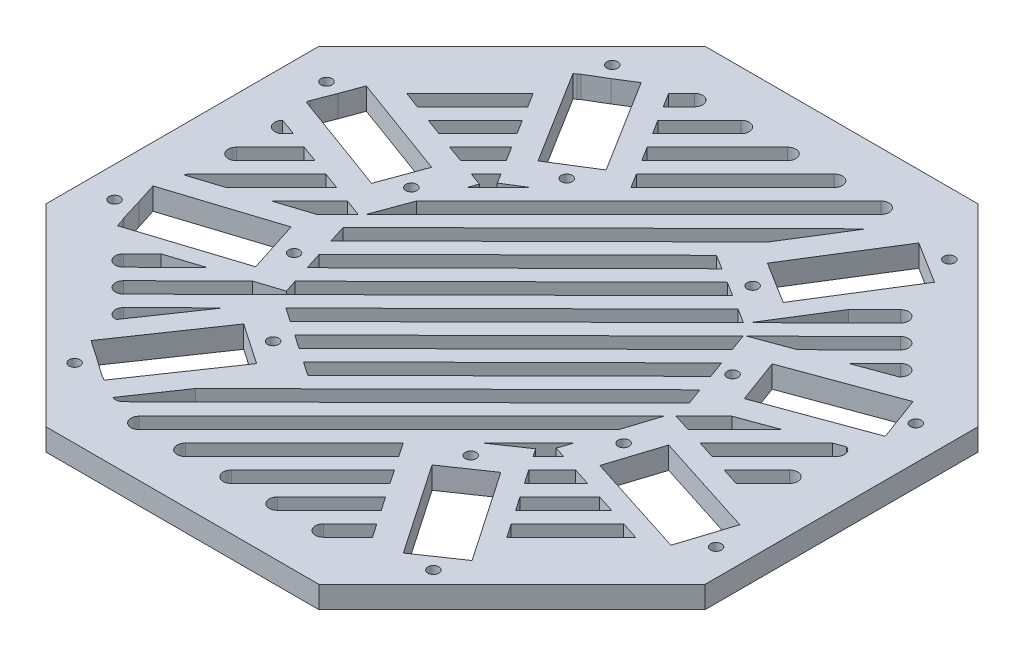
SolidWorks part; units mm, degrees
other "Camera1"
ref_plane "Front Plane" through (0, 0, 0) normal (0, 0, 1) x (1, 0, 0)
ref_plane "Top Plane" through (0, 0, 0) normal (0, 1, 0) x (1, 0, 0)
ref_plane "Right Plane" through (0, 0, 0) normal (1, 0, 0) x (0, 0, -1)
sketch "Sketch" plane through (0, 0, 0) normal (0, 1, 0) x (1, 0, 0)
  line L0 (0, 0) -> (60, 0) construction
  line L1 (0, 0) -> (60, 24.8528) construction
  line L2 (-6.8563, 54.06) -> (-15.6607, 52.1942)
  line L3 (60, 24.8528) -> (24.8528, 60)
  line L4 (24.8528, 60) -> (-24.8528, 60)
  line L5 (-24.8528, 60) -> (-60, 24.8528)
  line L6 (-60, 24.8528) -> (-60, -24.8528)
  line L7 (-60, -24.8528) -> (-24.8528, -60)
  line L8 (-24.8528, -60) -> (24.8528, -60)
  line L9 (24.8528, -60) -> (60, -24.8528)
  line L10 (60, -24.8528) -> (60, 24.8528)
  line L11 (50.7227, 19.9174) -> (46.7526, 27.9944)
  line L12 (46.7526, 27.9944) -> (41.5072, 35.3079)
  line L13 (41.5072, 35.3079) -> (35.1296, 41.6582)
  line L14 (35.1296, 41.6582) -> (27.7938, 46.8721)
  line L15 (27.7938, 46.8721) -> (19.6998, 50.8076)
  line L16 (19.6998, 50.8076) -> (11.0685, 53.3571)
  line L17 (11.0685, 53.3571) -> (2.1352, 54.4512)
  line L18 (2.1352, 54.4512) -> (-6.8563, 54.06)
  line L19 (-15.6607, 52.1942) -> (-24.038, 48.9047)
  line L20 (-24.038, 48.9047) -> (-31.7596, 44.2811)
  line L21 (-31.7596, 44.2811) -> (-38.6149, 38.4497)
  line L22 (-38.6149, 38.4497) -> (-44.4169, 31.5695)
  line L23 (-44.4169, 31.5695) -> (-49.0072, 23.8282)
  line L24 (-49.0072, 23.8282) -> (-52.2608, 15.4369)
  line L25 (-52.2608, 15.4369) -> (-54.0889, 6.6245)
  line L26 (-54.0889, 6.6245) -> (-54.4415, -2.3686)
  line L27 (-54.4415, -2.3686) -> (-53.3092, -11.2971)
  line L28 (-53.3092, -11.2971) -> (-50.7227, -19.9174)
  line L29 (-50.7227, -19.9174) -> (-46.7526, -27.9944)
  line L30 (-46.7526, -27.9944) -> (-41.5072, -35.3079)
  line L31 (-41.5072, -35.3079) -> (-35.1296, -41.6582)
  line L32 (-35.1296, -41.6582) -> (-27.7938, -46.8721)
  line L33 (-27.7938, -46.8721) -> (-19.6998, -50.8076)
  line L34 (-19.6998, -50.8076) -> (-11.0685, -53.3571)
  line L35 (-11.0685, -53.3571) -> (-2.1352, -54.4512)
  line L36 (-2.1352, -54.4512) -> (6.8563, -54.06)
  line L37 (6.8563, -54.06) -> (15.6607, -52.1942)
  line L38 (15.6607, -52.1942) -> (24.038, -48.9047)
  line L39 (24.038, -48.9047) -> (31.7596, -44.2811)
  line L40 (31.7596, -44.2811) -> (38.6149, -38.4497)
  line L41 (38.6149, -38.4497) -> (44.4169, -31.5695)
  line L42 (44.4169, -31.5695) -> (49.0072, -23.8282)
  line L43 (49.0072, -23.8282) -> (52.2608, -15.4369)
  line L44 (52.2608, -15.4369) -> (54.0889, -6.6245)
  line L45 (54.0889, -6.6245) -> (54.4415, 2.3686)
  line L46 (54.4415, 2.3686) -> (53.3092, 11.2971)
  line L47 (53.3092, 11.2971) -> (50.7227, 19.9174)
  line L48 (0.3388, 60) -> (0.3388, -60) construction
  line L49 (-24.9398, 48.451) -> (-32.5744, 43.6852)
  line L50 (-24.9398, 48.451) -> (-14.3492, 31.4852)
  line L51 (-32.5744, 43.6852) -> (-21.9838, 26.7194)
  line L52 (-14.3492, 31.4852) -> (-21.9838, 26.7194)
  line L53 (-49.4402, 22.9163) -> (-52.3773, 14.904)
  line L54 (-49.4402, 22.9163) -> (-30.6621, 16.0327)
  line L55 (-52.3773, 14.904) -> (-33.5992, 8.0205)
  line L56 (-30.6621, 16.0327) -> (-33.5992, 8.0205)
  line L57 (-53.0908, -12.2827) -> (-50.0451, -21.7898)
  line L58 (-53.0908, -12.2827) -> (-34.0442, -6.181)
  line L59 (-50.0451, -21.7898) -> (-30.9986, -15.6881)
  line L60 (-34.0442, -6.181) -> (-30.9986, -15.6881)
  line L61 (-34.3519, -42.3018) -> (-26.9207, -47.379)
  line L62 (-34.3519, -42.3018) -> (-23.0692, -25.7881)
  line L63 (-26.9207, -47.379) -> (-15.6381, -30.8653)
  line L64 (-23.0692, -25.7881) -> (-15.6381, -30.8653)
  line L65 (27.5983, -47.379) -> (16.3156, -30.8653)
  line L66 (23.7468, -25.7881) -> (16.3156, -30.8653)
  line L67 (35.0295, -42.3018) -> (23.7468, -25.7881)
  line L68 (35.0295, -42.3018) -> (27.5983, -47.379)
  line L69 (53.0549, 14.904) -> (34.2768, 8.0205)
  line L70 (31.3397, 16.0327) -> (34.2768, 8.0205)
  line L71 (50.1178, 22.9163) -> (31.3397, 16.0327)
  line L72 (50.1178, 22.9163) -> (53.0549, 14.904)
  line L73 (33.252, 43.6852) -> (22.6614, 26.7194)
  line L74 (15.0268, 31.4852) -> (22.6614, 26.7194)
  line L75 (25.6174, 48.451) -> (15.0268, 31.4852)
  line L76 (25.6174, 48.451) -> (33.252, 43.6852)
  line L77 (50.7227, -21.7898) -> (31.6761, -15.6881)
  line L78 (34.7218, -6.181) -> (31.6761, -15.6881)
  line L79 (53.7683, -12.2827) -> (34.7218, -6.181)
  line L80 (53.7683, -12.2827) -> (50.7227, -21.7898)
  line L81 (-30.6621, 16.0327) -> (-29.2854, 19.7884) construction
  line L82 (-29.2854, 19.7884) -> (-23.652, 17.7233) construction
  line L83 (-33.5992, 8.0205) -> (-35.1364, 3.827) construction
  line L84 (-35.1364, 3.827) -> (-29.503, 1.7619) construction
  line L85 (-52.3773, 14.904) -> (-53.9145, 10.7105) construction
  line L86 (-53.9145, 10.7105) -> (-59.548, 12.7756) construction
  line L87 (-21.9838, 26.7194) -> (-25.377, 24.6013) construction
  line L88 (-25.377, 24.6013) -> (-22.1998, 19.5115) construction
  line L89 (-14.3492, 31.4852) -> (-10.9561, 33.6033) construction
  line L90 (-10.9561, 33.6033) -> (-7.7789, 28.5135) construction
  line L91 (-24.9398, 48.451) -> (-21.5467, 50.5691) construction
  line L92 (-21.5467, 50.5691) -> (-24.1943, 54.8106) construction
  line L93 (15.0268, 31.4852) -> (11.146, 33.9076) construction
  line L94 (11.146, 33.9076) -> (7.9689, 28.8179) construction
  line L95 (22.6614, 26.7194) -> (25.567, 24.9056) construction
  line L96 (25.567, 24.9056) -> (22.3898, 19.8159) construction
  line L97 (33.252, 43.6852) -> (36.1576, 41.8715) construction
  line L98 (36.1576, 41.8715) -> (38.8052, 46.1129) construction
  line L99 (31.3397, 16.0327) -> (29.8827, 20.0073) construction
  line L100 (29.8827, 20.0073) -> (24.2493, 17.9422) construction
  line L101 (34.2768, 8.0205) -> (35.7337, 4.0459) construction
  line L102 (35.7337, 4.0459) -> (30.1003, 1.9809) construction
  line L103 (53.0549, 14.904) -> (54.5118, 10.9295) construction
  line L104 (54.5118, 10.9295) -> (60.1453, 12.9945) construction
  line L105 (31.6761, -15.6881) -> (30.6927, -18.7581) construction
  line L106 (30.6927, -18.7581) -> (24.9787, -16.9276) construction
  line L107 (34.7218, -6.181) -> (35.8791, -2.5685) construction
  line L108 (35.8791, -2.5685) -> (30.1651, -0.738) construction
  line L109 (53.7683, -12.2827) -> (54.9256, -8.6702) construction
  line L110 (54.9256, -8.6702) -> (59.6872, -10.1956) construction
  line L111 (23.7468, -25.7881) -> (26.5876, -23.8472) construction
  line L112 (26.5876, -23.8472) -> (23.2028, -18.893) construction
  line L113 (16.3156, -30.8653) -> (12.551, -33.4374) construction
  line L114 (12.551, -33.4374) -> (9.1662, -28.4833) construction
  line L115 (27.5983, -47.379) -> (23.8336, -49.9511) construction
  line L116 (23.8336, -49.9511) -> (26.6543, -54.0795) construction
  line L117 (-23.0692, -25.7881) -> (-19.6844, -20.834) construction
  line L118 (-19.6844, -20.834) -> (-22.9872, -18.5774) construction
  line L119 (-15.6381, -30.8653) -> (-12.2533, -25.9112) construction
  line L120 (-12.2533, -25.9112) -> (-8.9506, -28.1677) construction
  line L121 (-34.3519, -42.3018) -> (-37.6546, -40.0452) construction
  line L122 (-37.6546, -40.0452) -> (-40.4753, -44.1736) construction
  line L123 (-53.0908, -12.2827) -> (-54.3111, -8.4734) construction
  line L124 (-54.3111, -8.4734) -> (-59.0727, -9.9988) construction
  line L125 (-34.0442, -6.181) -> (-35.2646, -2.3717) construction
  line L126 (-35.2646, -2.3717) -> (-29.5506, -0.5412) construction
  line L127 (-30.9986, -15.6881) -> (-30.0782, -18.5612) construction
  line L128 (-30.0782, -18.5612) -> (-24.3642, -16.7307) construction
  line L129 (-24.1943, 54.8106) -> (-7.7789, 28.5135)
  line L130 (-24.1943, 54.8106) -> (-38.6153, 45.8086)
  line L131 (-7.7789, 28.5135) -> (-22.1998, 19.5115)
  line L132 (-38.6153, 45.8086) -> (-22.1998, 19.5115)
  line L133 (7.9689, 28.8179) -> (22.3898, 19.8159)
  line L134 (7.9689, 28.8179) -> (24.3843, 55.1149)
  line L135 (22.3898, 19.8159) -> (38.8052, 46.1129)
  line L136 (24.3843, 55.1149) -> (38.8052, 46.1129)
  line L137 (24.2493, 17.9422) -> (30.1003, 1.9809)
  line L138 (24.2493, 17.9422) -> (54.2942, 28.9559)
  line L139 (30.1003, 1.9809) -> (60.1453, 12.9945)
  line L140 (54.2942, 28.9559) -> (60.1453, 12.9945)
  line L141 (24.9787, -16.9276) -> (30.1651, -0.738)
  line L142 (24.9787, -16.9276) -> (54.5008, -26.3852)
  line L143 (30.1651, -0.738) -> (59.6872, -10.1956)
  line L144 (54.5008, -26.3852) -> (59.6872, -10.1956)
  line L145 (23.2028, -18.893) -> (9.1662, -28.4833)
  line L146 (23.2028, -18.893) -> (40.6909, -44.4892)
  line L147 (9.1662, -28.4833) -> (26.6543, -54.0795)
  line L148 (40.6909, -44.4892) -> (26.6543, -54.0795)
  line L149 (-40.4753, -44.1736) -> (-22.9872, -18.5774)
  line L150 (-40.4753, -44.1736) -> (-26.4387, -53.7639)
  line L151 (-22.9872, -18.5774) -> (-8.9506, -28.1677)
  line L152 (-26.4387, -53.7639) -> (-8.9506, -28.1677)
  line L153 (-59.0727, -9.9988) -> (-29.5506, -0.5412)
  line L154 (-59.0727, -9.9988) -> (-53.8863, -26.1883)
  line L155 (-29.5506, -0.5412) -> (-24.3642, -16.7307)
  line L156 (-53.8863, -26.1883) -> (-24.3642, -16.7307)
  line L157 (-59.548, 12.7756) -> (-29.503, 1.7619)
  line L158 (-59.548, 12.7756) -> (-53.6969, 28.737)
  line L159 (-29.503, 1.7619) -> (-23.652, 17.7233)
  line L160 (-53.6969, 28.737) -> (-23.652, 17.7233)
  line L161 (-32.1307, 12.0266) -> (-29.314, 10.9941) construction
  line L162 (-50.9088, 18.9102) -> (-53.7255, 19.9427) construction
  line L163 (-18.1665, 29.1023) -> (-16.5779, 26.5574) construction
  line L164 (-28.7571, 46.0681) -> (-30.3457, 48.613) construction
  line L165 (18.8441, 29.1023) -> (17.2555, 26.5574) construction
  line L166 (29.4347, 46.0681) -> (31.0233, 48.613) construction
  line L167 (32.8082, 12.0266) -> (29.3942, 10.7751) construction
  line L168 (51.5863, 18.9102) -> (53.8057, 19.7237) construction
  line L169 (52.2455, -17.0362) -> (55.1025, -17.9515) construction
  line L170 (33.199, -10.9345) -> (30.342, -10.0193) construction
  line L171 (31.3139, -44.8404) -> (33.0063, -47.3174) construction
  line L172 (20.0312, -28.3267) -> (18.3388, -25.8496) construction
  line L173 (-30.6363, -44.8404) -> (-32.3287, -47.3174) construction
  line L174 (-19.3537, -28.3267) -> (-17.6613, -25.8496) construction
  line L175 (-51.5679, -17.0362) -> (-54.4249, -17.9515) construction
  line L176 (-32.5214, -10.9345) -> (-29.6644, -10.0193) construction
  line L177 (24.8528, 60) -> (0, 0) construction
  line L178 (60, -24.8528) -> (0, 0) construction
  line L179 (0, 0) -> (24.8528, -60) construction
  line L180 (-24.8528, -60) -> (0, 0) construction
  line L181 (0, 0) -> (-60, -24.8528) construction
  line L182 (-60, 24.8528) -> (0, 0) construction
  line L183 (0, 0) -> (-24.8528, 60) construction
  line L184 (-19.8494, 50.5494) -> (20.2308, 50.5494) construction
  line L185 (20.2308, 50.5494) -> (50.7227, 19.9174) construction
  line L186 (50.7227, -21.7898) -> (50.7227, 19.9174) construction
  line L187 (50.7227, -21.7898) -> (19.8494, -50.5494) construction
  line L188 (19.8494, -50.5494) -> (-20.2308, -50.5494) construction
  line L189 (-20.2308, -50.5494) -> (-50.7227, -19.9174) construction
  line L190 (-50.7227, -19.9174) -> (-50.1861, 20.7878) construction
  line L191 (-50.1861, 20.7878) -> (-19.8494, 50.5494) construction
  line L192 (-35.5159, -35.194) -> (35.5159, 35.194) construction
  line L193 (-36.5718, -34.1285) -> (34.4601, 36.2595)
  line L194 (-34.4601, -36.2595) -> (36.5718, 34.1285)
  line L195 (-31.2733, -39.4367) -> (39.7586, 30.9514) construction
  line L196 (-32.3291, -38.3712) -> (38.7028, 32.0169)
  line L197 (-30.2175, -40.5021) -> (40.8144, 29.8859)
  line L198 (-27.0306, -43.6793) -> (44.0012, 26.7087) construction
  line L199 (-28.0865, -42.6138) -> (42.9454, 27.7742)
  line L200 (-25.9748, -44.7448) -> (45.057, 25.6433)
  line L201 (-22.788, -47.9219) -> (48.2439, 22.4661) construction
  line L202 (-23.8438, -46.8565) -> (47.188, 23.5316)
  line L203 (-21.7322, -48.9874) -> (49.2997, 21.4006)
  line L204 (-39.7586, -30.9514) -> (31.2733, 39.4367) construction
  line L205 (-40.8144, -29.8859) -> (30.2175, 40.5021)
  line L206 (-38.7028, -32.0169) -> (32.3291, 38.3712)
  line L207 (-44.0012, -26.7087) -> (27.0306, 43.6793) construction
  line L208 (-45.057, -25.6433) -> (25.9748, 44.7448)
  line L209 (-42.9454, -27.7742) -> (28.0865, 42.6138)
  line L210 (-48.2439, -22.4661) -> (22.788, 47.9219) construction
  line L211 (-49.2997, -21.4006) -> (21.7322, 48.9874)
  line L212 (-47.188, -23.5316) -> (23.8438, 46.8565)
  line L213 (-16.9781, -50.9084) -> (50.7227, 16.7923) construction
  line L216 (0, 0) -> (38.2978, -38.7195) construction
  line L217 (0, 0) -> (4.2193, -4.2658) construction
  line L218 (4.2193, -4.2658) -> (8.4387, -8.5316) construction
  line L219 (8.4387, -8.5316) -> (12.658, -12.7974) construction
  line L220 (12.658, -12.7974) -> (16.8723, -17.0581) construction
  line L221 (16.8723, -17.0581) -> (21.0967, -21.329) construction
  line L222 (21.0967, -21.329) -> (25.3161, -25.5948) construction
  line L223 (25.3161, -25.5948) -> (29.5354, -29.8606) construction
  line L224 (29.5354, -29.8606) -> (33.7548, -34.1264) construction
  line L225 (-18.036, -49.8506) -> (49.6648, 17.8502)
  line L226 (-15.9202, -51.9663) -> (51.7805, 15.7344)
  line L227 (-8.5292, -50.9549) -> (50.7227, 8.2969) construction
  line L228 (-9.5899, -49.8943) -> (49.662, 9.3576)
  line L229 (-7.4685, -52.0156) -> (51.7833, 7.2362)
  line L230 (-0.0905, -51.0014) -> (50.7227, -0.1882) construction
  line L231 (-1.1512, -49.9407) -> (49.662, 0.8724)
  line L232 (0.9702, -52.0621) -> (51.7833, -1.2489)
  line L233 (8.3482, -51.0479) -> (50.7227, -8.6734) construction
  line L234 (7.2875, -49.9872) -> (49.662, -7.6127)
  line L235 (9.4089, -52.1085) -> (51.7833, -9.7341)
  line L236 (16.7869, -51.0943) -> (50.7227, -17.1585) construction
  line L237 (15.7262, -50.0337) -> (49.662, -16.0979)
  line L238 (17.8475, -52.155) -> (51.7833, -18.2192)
  line L239 (0, 0) -> (-38.5256, 38.5256) construction
  line L240 (0, 0) -> (-4.2426, 4.2426) construction
  line L241 (-4.2426, 4.2426) -> (-8.4853, 8.4853) construction
  line L242 (-8.4853, 8.4853) -> (-12.7279, 12.7279) construction
  line L243 (-12.7279, 12.7279) -> (-16.9706, 16.9706) construction
  line L244 (-12.7279, 12.7279) -> (-16.9706, 16.9706) construction
  line L245 (-50.5494, -16.6083) -> (16.6083, 50.5494) construction
  line L246 (-51.6101, -15.5476) -> (15.5476, 51.6101)
  line L247 (-49.4888, -17.669) -> (17.669, 49.4888)
  line L248 (-16.9706, 16.9706) -> (-21.2132, 21.2132) construction
  line L249 (-50.5494, -8.123) -> (8.123, 50.5494) construction
  line L250 (-51.6101, -7.0624) -> (7.0624, 51.6101)
  line L251 (-49.4888, -9.1837) -> (9.1837, 49.4888)
  line L252 (-21.2132, 21.2132) -> (-25.4558, 25.4558) construction
  line L253 (-50.5494, 0.3623) -> (-0.3623, 50.5494) construction
  line L254 (-51.6101, 1.4229) -> (-1.4229, 51.6101)
  line L255 (-49.4888, -0.6984) -> (0.6984, 49.4888)
  line L256 (-25.4558, 25.4558) -> (-29.6985, 29.6985) construction
  line L257 (-50.5494, 8.8476) -> (-8.8476, 50.5494) construction
  line L258 (-51.6101, 9.9082) -> (-9.9082, 51.6101)
  line L259 (-49.4888, 7.7869) -> (-7.7869, 49.4888)
  line L260 (-29.6985, 29.6985) -> (-33.9411, 33.9411) construction
  line L261 (-50.5494, 17.3328) -> (-17.3328, 50.5494) construction
  line L262 (-51.6101, 18.3935) -> (-18.3935, 51.6101)
  line L263 (-49.4888, 16.2722) -> (-16.2722, 49.4888)
  circle A0 centre (0, 0) radius 60 construction
  circle A1 centre (0, 0) radius 54.3069 construction
  circle A2 centre (-54.4249, -17.9515) radius 1
  circle A3 centre (-29.6644, -10.0193) radius 1
  circle A4 centre (-29.314, 10.9941) radius 1
  circle A5 centre (-53.7255, 19.9427) radius 1
  circle A6 centre (-30.3457, 48.613) radius 1
  circle A7 centre (-16.5779, 26.5574) radius 1
  circle A8 centre (31.0233, 48.613) radius 1
  circle A9 centre (17.2555, 26.5574) radius 1
  circle A10 centre (53.8057, 19.7237) radius 1
  circle A11 centre (29.3942, 10.7751) radius 1
  circle A12 centre (55.1025, -17.9515) radius 1
  circle A13 centre (30.342, -10.0193) radius 1
  circle A14 centre (33.0063, -47.3174) radius 1
  circle A15 centre (18.3388, -25.8496) radius 1
  circle A16 centre (-17.6613, -25.8496) radius 1
  circle A17 centre (-32.3287, -47.3174) radius 1
  arc A18 (-36.5718, -34.1285) -> (-34.4601, -36.2595) centre (-35.5159, -35.194) ccw
  arc A19 (36.5718, 34.1285) -> (34.4601, 36.2595) centre (35.5159, 35.194) ccw
  arc A20 (-32.3291, -38.3712) -> (-30.2175, -40.5021) centre (-31.2733, -39.4367) ccw
  arc A21 (40.8144, 29.8859) -> (38.7028, 32.0169) centre (39.7586, 30.9514) ccw
  arc A22 (-28.0865, -42.6138) -> (-25.9748, -44.7448) centre (-27.0306, -43.6793) ccw
  arc A23 (45.057, 25.6433) -> (42.9454, 27.7742) centre (44.0012, 26.7087) ccw
  arc A24 (-23.8438, -46.8565) -> (-21.7322, -48.9874) centre (-22.788, -47.9219) ccw
  arc A25 (49.2997, 21.4006) -> (47.188, 23.5316) centre (48.2439, 22.4661) ccw
  arc A26 (-40.8144, -29.8859) -> (-38.7028, -32.0169) centre (-39.7586, -30.9514) ccw
  arc A27 (32.3291, 38.3712) -> (30.2175, 40.5021) centre (31.2733, 39.4367) ccw
  arc A28 (-45.057, -25.6433) -> (-42.9454, -27.7742) centre (-44.0012, -26.7087) ccw
  arc A29 (28.0865, 42.6138) -> (25.9748, 44.7448) centre (27.0306, 43.6793) ccw
  arc A30 (-49.2997, -21.4006) -> (-47.188, -23.5316) centre (-48.2439, -22.4661) ccw
  arc A31 (23.8438, 46.8565) -> (21.7322, 48.9874) centre (22.788, 47.9219) ccw
  arc A34 (-18.036, -49.8506) -> (-15.9202, -51.9663) centre (-16.9781, -50.9084) ccw
  arc A35 (51.7805, 15.7344) -> (49.6648, 17.8502) centre (50.7227, 16.7923) ccw
  arc A36 (-9.5899, -49.8943) -> (-7.4685, -52.0156) centre (-8.5292, -50.9549) ccw
  arc A37 (51.7833, 7.2362) -> (49.662, 9.3576) centre (50.7227, 8.2969) ccw
  arc A38 (-1.1512, -49.9407) -> (0.9702, -52.0621) centre (-0.0905, -51.0014) ccw
  arc A39 (51.7833, -1.2489) -> (49.662, 0.8724) centre (50.7227, -0.1882) ccw
  arc A40 (7.2875, -49.9872) -> (9.4089, -52.1085) centre (8.3482, -51.0479) ccw
  arc A41 (51.7833, -9.7341) -> (49.662, -7.6127) centre (50.7227, -8.6734) ccw
  arc A42 (15.7262, -50.0337) -> (17.8475, -52.155) centre (16.7869, -51.0943) ccw
  arc A43 (51.7833, -18.2192) -> (49.662, -16.0979) centre (50.7227, -17.1585) ccw
  arc A44 (-51.6101, -15.5476) -> (-49.4888, -17.669) centre (-50.5494, -16.6083) ccw
  arc A45 (17.669, 49.4888) -> (15.5476, 51.6101) centre (16.6083, 50.5494) ccw
  arc A46 (-51.6101, -7.0624) -> (-49.4888, -9.1837) centre (-50.5494, -8.123) ccw
  arc A47 (9.1837, 49.4888) -> (7.0624, 51.6101) centre (8.123, 50.5494) ccw
  arc A48 (-51.6101, 1.4229) -> (-49.4888, -0.6984) centre (-50.5494, 0.3623) ccw
  arc A49 (0.6984, 49.4888) -> (-1.4229, 51.6101) centre (-0.3623, 50.5494) ccw
  arc A50 (-51.6101, 9.9082) -> (-49.4888, 7.7869) centre (-50.5494, 8.8476) ccw
  arc A51 (-7.7869, 49.4888) -> (-9.9082, 51.6101) centre (-8.8476, 50.5494) ccw
  arc A52 (-51.6101, 18.3935) -> (-49.4888, 16.2722) centre (-50.5494, 17.3328) ccw
  arc A53 (-16.2722, 49.4888) -> (-18.3935, 51.6101) centre (-17.3328, 50.5494) ccw
  point P196 (0, 0)
  point P205 (4.2426, -4.2426)
  point P212 (8.4853, -8.4853)
  point P219 (12.7279, -12.7279)
  point P225 (-4.2426, 4.2426)
  point P232 (-8.4853, 8.4853)
  point P239 (-12.7279, 12.7279)
  point P245 (16.8723, -17.0581)
  point P260 (21.0967, -21.329)
  point P268 (25.3161, -25.5948)
  point P275 (29.5354, -29.8606)
  point P281 (33.7548, -34.1264)
  point P294 (-16.9706, 16.9706)
  point P302 (-21.2132, 21.2132)
  point P310 (-25.4558, 25.4558)
  point P318 (-29.6985, 29.6985)
  point P326 (-33.9411, 33.9411)
  dimension "D5" = 4
  dimension "D1" = 9
  dimension "D2" = 20
  dimension "D3" = 20
  dimension "D4" = 20
  dimension "D6" = 4
extrude "Boss-Extrude2" add sketch "Sketch" along normal blind 4 contours A53 L19 L2 L18 L17 L16 A45 L15 L134 L136 L3 L4 L5 L6 L7 L8 L9 L148 L147 L38 L238 A42 L37 L36 L35 L34 L226 A34 L33 A24 L152 L150 L149 L31 L30 L29 L156 L154 L153 L27 L26 L25 L157 L158 L160 L23 L22 L21 | L130 L132 L21 L51 L49 L20 L50 L19 L129 A6 | A52 L262 L53 L54 L24 L23 L160 L158 L157 L25 L55 A5 | L138 L140 L10 L3 L135 L13 L12 L11 | A25 L71 L72 L69 L47 L46 L139 L10 L140 L138 L11 A10 | L40 L146 L9 L10 L139 L46 L45 L44 L143 L144 L142 L42 L41 | A43 L80 L77 L43 L42 L142 L144 L143 L44 L79 A12 | L148 L9 L146 L40 L67 L68 L65 L39 L38 L147 A14 | A24 L33 L63 L61 L32 L62 L31 L149 L150 L152 A17 | A44 L57 L58 L28 L27 L153 L154 L156 L29 A30 L59 A2 | A31 L15 L75 L76 L73 L14 L13 L135 L3 L136 L134 A8 | A23 L200 L138 L11 L12 L13 L135 L193 A19 L194 L133 L151 L196 L137 A21 L197 L199 | A53 L263 L129 L258 A51 L259 L254 A49 L255 L250 A47 L251 L131 L159 L246 A45 L16 L17 L18 L2 L19 | A45 L247 L159 L157 L153 L155 L211 L134 L15 L16 | L160 L262 L132 L21 L22 L23 | L263 L160 L258 L132 | L259 L160 L254 L132 | L255 L160 L250 L132 | A50 L157 L25 L26 L27 L153 A46 L250 L255 A48 L254 L259 | L251 L153 L246 L157 | L238 L146 L40 L41 L42 L142 | L146 L237 L142 L235 | L146 L234 L142 L232 | L146 L231 L142 L229 | A42 L237 L147 L235 A40 L234 L232 A38 L231 L229 A36 L228 L145 L141 L226 L34 L35 L36 L37 L38 | A34 L225 L141 L143 L139 L137 L203 A24 L33 L34 | L152 L202 L137 L200 L151 | L151 L199 L137 L197 | A28 L208 L156 L29 L30 L31 L149 A18 L193 L151 L133 L206 A26 L205 L209 | L209 L155 L205 L133 | L212 L155 L208 L133 L134 | L143 L228 L139 L226 | A41 L143 L44 L45 L46 L139 A37 L229 L231 A39 L232 | A31 L15 L134 L211 | L15 A31 | L212 A31 L15 L211 L134 | A31 L212 L134 L133 L208 L75 L15 | L133 L209 L74 L75 L208 | A9 L205 L74 L209 L133 | A9 L205 L133 L206 L74 | A27 L206 L73 L74 L133 L193 L135 L13 L14 | L133 L194 L135 L193 | L194 L133 L135 | L71 A25 L11 | L11 A25 L202 L71 | A25 L11 L138 L200 L71 L202 | A11 L200 L70 L71 L138 L199 L137 | L137 L199 L138 L197 | L137 L197 L138 L196 | L137 L196 L138 | A11 L200 L137 L202 L70 | L137 L203 L69 L70 L202 | L139 L225 L69 L203 L137 | L139 L226 L69 L225 | A37 L139 L46 L47 L69 L226 L228 | L139 A37 L228 | A41 L143 L232 L79 L234 | A41 L235 L79 L44 L143 | L235 A41 L143 L234 L79 | L79 L232 L143 L231 | L79 L231 L143 L229 | A13 L228 L141 L142 L229 L78 L79 L143 | A13 L228 L143 L226 L141 | L141 L226 L143 L225 | L141 L225 L143 | L142 L231 L77 L78 L229 | L142 L232 L77 L231 | L142 L234 L77 L232 | L142 L235 L77 L234 | L142 L237 L77 L235 | L238 L142 L42 L43 L77 | L142 L238 L77 L237 | A15 L229 L146 L145 L228 L147 | L147 L228 L145 | A15 L229 L147 L231 L65 L66 L146 | L67 L232 L146 L231 L66 | L67 L234 L146 L232 | L67 L235 L146 L234 | L67 L237 L146 L235 | L67 L238 L146 L237 | L238 L67 L40 L146 | L238 L147 L38 L39 L65 | L147 L238 L65 L237 | L147 L237 L65 L235 | L147 L235 L65 L234 | L147 L234 L65 L232 | L147 L232 L65 L231 | L238 L38 L147 | L33 A24 L152 | L202 A24 L33 L152 | A24 L202 L152 L151 L200 L63 L33 | A20 L196 L62 L64 L151 L194 A18 L149 L31 L32 | L196 A20 L62 | L149 A18 L194 L151 L193 | L63 L200 L151 L199 L64 | L64 L199 L151 L197 | L64 L197 L151 L196 A16 | L149 L193 L151 | L209 L156 L205 L155 | L205 L156 L155 | A3 L208 L60 L59 L156 L209 L155 | A30 L29 L156 L208 L59 L212 | L59 A30 L29 L212 | L29 A30 | A30 L59 L29 | L57 A44 L28 | A3 L208 L155 L212 L60 | L60 L212 L155 L211 | L247 L58 L60 L211 L155 L153 | L58 L247 L153 L246 | A46 L153 L27 L28 L58 L246 L251 | L153 A46 L251 | L247 L157 L159 | L157 L247 L159 L246 | A4 L251 L157 L246 L159 | A4 L251 L159 L160 L250 L56 L55 L157 | L255 L157 L250 L55 | L157 L255 L55 L254 | L259 L157 L254 L55 | L258 A50 L157 L259 L55 | A50 L258 L55 L25 L157 | L255 L54 L56 L250 L160 | L54 L255 L160 L254 | L259 L54 L254 L160 | L54 L259 L160 L258 | L263 L54 L258 L160 | L54 L263 L160 L262 | L54 L262 L160 L23 L24 | L262 A52 L24 L53 | L251 L131 L129 | A7 L250 L132 L131 L251 L129 | A7 L250 L129 L255 L50 L52 L51 L132 | L132 L255 L51 L254 | L259 L132 L254 L51 | L132 L259 L51 L258 | L263 L132 L258 L51 | L132 L263 L51 L262 | L132 L262 L51 L21 | L50 L262 L129 L19 L20 | L263 L50 L258 L129 | L259 L50 L254 L129 | L50 L255 L129 L254 | L50 L263 L129 L262 | L129 L262 L19 region at (-5.2382, 0, -41.4385) region at (-11.5819, 0, -54.6531) region at (-20.3787, 0, -50.0306) region at (-22.8906, 0, -48.3651) region at (-22.7016, 0, -49.6682) region at (-21.3712, 0, -46.5111) region at (-19.7406, 0, -43.899) region at (-4.851, 0, -24.8443) region at (-30.093, 0, -8.2521) region at (-29.7507, 0, -4.7509) region at (-32.8662, 0, -40.3303) region at (-30.8064, 0, -37.0759) region at (-16.4795, 0, -38.6748) region at (-29.1758, 0, -34.4638) region at (22.998, 0, -52.4701) region at (20.7639, 0, -48.5368) region at (-29.5313, 0, -2.1035) region at (-30.8938, 0, -11.4763) region at (-38.9517, 0, 0.6372) region at (-40.0369, 0, -33.1522) region at (-14.849, 0, -36.0627) region at (-27.5453, 0, -31.8517) region at (-35.317, 0, -28.3786) region at (23.3773, 0, -49.1339) region at (19.1678, 0, -43.9493) region at (-11.8525, 0, -27.1151) region at (-20.4337, 0, -20.8478) region at (-47.6475, 0, 8.4507) region at (-39.8969, 0, 5.9558) region at (-47.2109, 0, -24.4045) region at (-44.6074, 0, -23.2748) region at (-18.0743, 0, -28.3287) region at (-25.9147, 0, -29.2396) region at (-41.5028, 0, -22.1368) region at (16.0364, 0, -37.1421) region at (-9.1996, 0, -12.0374) region at (-33.9726, 0, 4.1279) region at (-31.1147, 0, 5.4922) region at (-29.3575, 0, -17.0503) region at (-25.9005, 0, -20.9209) region at (-45.5872, 0, 0.6979) region at (-39.0346, 0, -7.6344) region at (-49.6869, 0, 7.9309) region at (-48.4188, 0, -25.2499) region at (-24.2842, 0, -26.6275) region at (-30.5963, 0, -24.6399) region at (-38.3982, 0, -20.9987) region at (-30.1134, 0, 8.5688) region at (47.8139, 0, -32.8222) region at (-32.1891, 0, -18.7226) region at (-42.1392, 0, -8.7725) region at (-53.119, 0, 12.0732) region at (-35.2937, 0, -19.8607) region at (13.4874, 0, -30.6011) region at (-26.8707, 0, 9.5987) region at (26.8751, 0, -31.4168) region at (18.1071, 0, -12.7508) region at (-45.2438, 0, -9.9106) region at (-51.5798, 0, -17.834) region at (-51.2051, 0, -12.4428)
extrude "Boss-Extrude3" add sketch "Sketch<4>" along normal blind 4 contours L206 A27 L73 | L143 A41 region at (30.2618, 0, -37.4811) region at (51.1411, 0, 7.3671)
sketch "Sketch<4>" plane through (0, 0, 0) normal (0, 1, 0) x (1, 0, 0) same geometry as "Sketch"
extrude "Boss-Extrude4" add sketch "Sketch<5>" along normal blind 4 contours L50 L259 L129 L258 region at (-18.1101, 0, -41.2869)
sketch "Sketch<5>" plane through (0, 0, 0) normal (0, 1, 0) x (1, 0, 0) same geometry as "Sketch"
extrude "Boss-Extrude5" add sketch "Sketch<6>" along normal blind 4 contours L80 A43 region at (52.1015, 0, 17.6003)
sketch "Sketch<6>" plane through (0, 0, 0) normal (0, 1, 0) x (1, 0, 0) same geometry as "Sketch"
